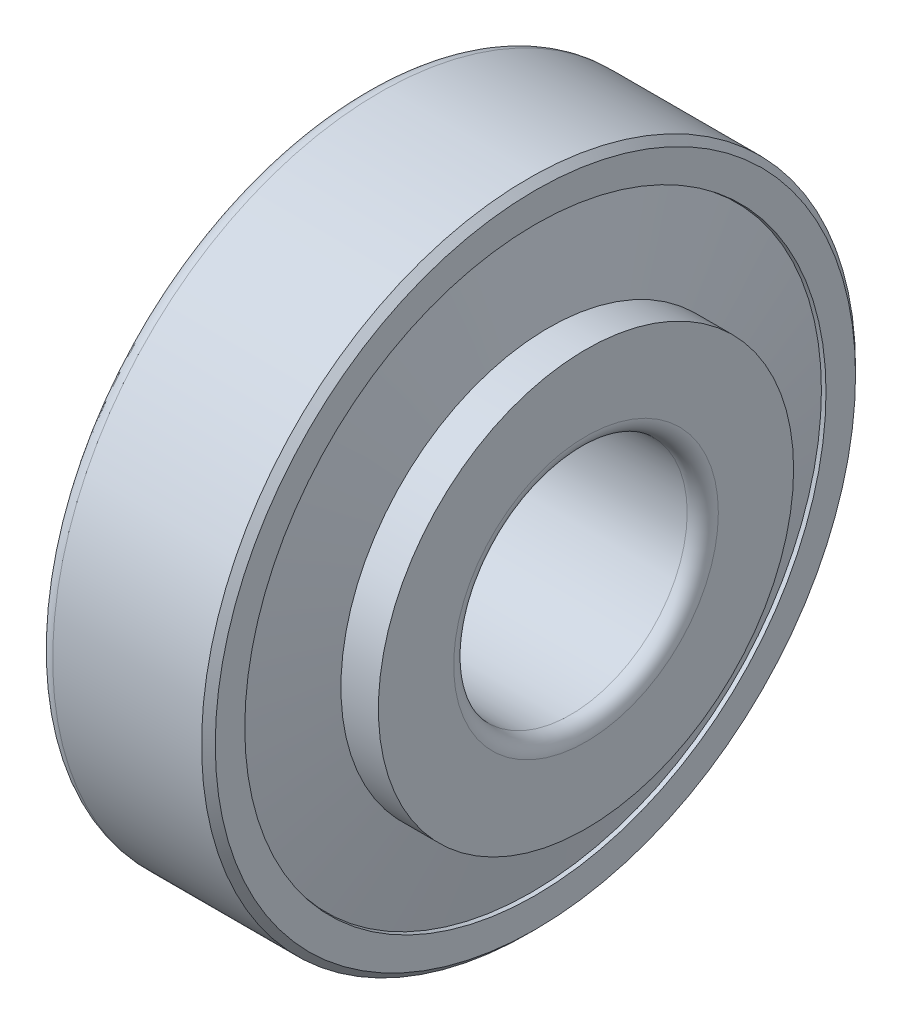
SolidWorks part; units mm, degrees
revolve "OuterRace" add sketch "OutRacSke" angle 360 about L5 other way angle 28.04 reverse direction yes
sketch "OutRacSke" plane through (0, 0, 0) normal (0, 0, 1) x (1, 0, 0)
  line L0 (-3.25, 18.6648) -> (-14.25, 16.636)
  line L1 (-14.25, 16.636) -> (-14.25, 20)
  line L2 (-13.25, 21) -> (-3.69, 21)
  line L3 (-3.69, 21) -> (-3.25, 20.56)
  line L4 (-3.25, 20.56) -> (-3.25, 18.6648)
  line L5 (-42.5, 0) -> (42.5, 0) construction
  arc A0 (-14.25, 20) -> (-13.25, 21) centre (-13.25, 20) cw
  dimension "D8" = 45
  dimension "Tangle" = 10.45
ref_plane "Plane1" through (0, 0, 0) normal (0, 0, 1) x (1, 0, 0)
ref_plane "Plane2" through (0, 0, 0) normal (0, 1, 0) x (1, 0, 0)
ref_plane "Plane3" through (0, 0, 0) normal (1, 0, 0) x (0, 0, -1)
sketch "Clipboard" plane through (0, 0, 0) normal (0, 0, 1) x (1, 0, 0)
  line L0 (0, 0) -> (10, 0) construction
  line L1 (0, 0) -> (33.2517, -1.1612)
  line L2 (0, 0) -> (14.9909, 0.5235)
  line L3 (0, 0) -> (41.9744, -1.4658)
  line L4 (0, 0) -> (-9.8985, -0.1728)
  line L5 (0, 0) -> (-6.075, 14.25)
  dimension "Roller_diameter" = 6.075
  dimension "cyl_len" = 9.9
sketch "RolDetSke" plane through (0, 0, 0) normal (0, 0, 1) x (1, 0, 0)
  line L0 (-12.6991, 13.9174) -> (-13.25, 16.9045)
  line L1 (-12.6991, 13.9174) -> (-2.9633, 15.7131)
  line L2 (-3.5142, 18.7002) -> (-2.9633, 15.7131)
  line L4 (-41.1331, 8.6731) -> (8.5425, 17.8351) construction
  line L5 (-3.5142, 18.7002) -> (-13.25, 16.9045)
  line L9 (-3.25, 18.6648) -> (-14.25, 16.636) construction
  dimension "Roller_diameter" = 6.075
  dimension "dy" = 16.9045
  dimension "D2" = 13.25
  dimension "cyl_len" = 9.9
revolve "RollerDetailed" [suppressed] add sketch "RolDetSke" angle 360 about L4 reverse direction yes
sketch "RolSimSke" plane through (0, 0, 0) normal (0, 0, 1) x (1, 0, 0)
  line L0 (0, 0) -> (-32, 0) construction
  line L1 (-13.25, 16.9045) -> (-3.5142, 18.7002)
  line L2 (-13.25, 16.9045) -> (-12.1481, 10.9303)
  line L3 (-12.1481, 10.9303) -> (-2.4123, 12.7259)
  line L4 (-3.5142, 18.7002) -> (-2.4123, 12.7259)
  dimension "Roller_diameter" = 6.075
  dimension "dy" = 16.9045
  dimension "dx" = 13.25
  dimension "Tangle" = 10.45
revolve "RollersSimplified" add sketch "RolSimSke" angle 360 about L0
ref_axis "Axis1" through (-50, 0, 0) along (1, 0, 0)
pattern_circular "RollersDetailed" [suppressed] count 2 every 180 about axis through (-50, 0, 0) along (1, 0, 0)
sketch "InsRacSke" plane through (0, 0, 0) normal (0, 0, 1) x (1, 0, 0)
  line L0 (-12.1986, 11.2341) -> (-13, 11.2341)
  line L1 (-14.25, 20) -> (-14.25, -20) construction
  line L2 (-13, 11.2341) -> (-13, 7.94)
  line L3 (-13, 7.94) -> (-12.56, 7.5)
  line L4 (-12.56, 7.5) -> (-1, 7.5)
  line L5 (0, 8.5) -> (0, 13.3334)
  line L6 (0, 13.3334) -> (-2.4068, 13.3334)
  line L7 (-2.4068, 13.3334) -> (-2.4068, 12.7259)
  line L8 (-2.4068, 12.7259) -> (-12.1426, 10.9303)
  line L9 (-12.1426, 10.9303) -> (-12.1986, 11.2341)
  line L10 (-42.5, 0) -> (42.5, 0) construction
  arc A0 (-1, 7.5) -> (0, 8.5) centre (-1, 8.5) ccw
  dimension "Tangle" = 10.45
  dimension "cyl_len" = 9.9
  dimension "dy" = 10.9303
  dimension "dx" = 12.1426
  dimension "D11" = 45
  dimension "D2" = 14.25
revolve "InnerRace" add sketch "InsRacSke" angle 360 about L10 reverse direction yes
sketch "CagSpiSke" plane through (0, 0, 0) normal (0, 0, 1) x (1, 0, 0)
  line L3 (-2.4765, 15.7187) -> (-12.6991, 13.8333)
  line L4 (-13.0239, 13.3616) -> (-12.877, 12.565)
  line L6 (-42.5, 0) -> (42.5, 0) construction
  arc A1 (-12.6991, 13.8333) -> (-13.0239, 13.3616) centre (-12.6256, 13.435) ccw
  dimension "Tangle" = 10.45
  dimension "radius" = 0.405
  dimension "dx" = 12.6991
  dimension "dy" = 13.8333
  dimension "offset" = 1.215
revolve "CageSpine" [suppressed] add sketch "CagSpiSke" angle 0.001 about L6 wall 1.0125
equation "\"OD@OutRacSke\" = \"Race_OD@Clipboard\""
equation "\"cup_SID@OutRacSke\" = \"Race_ID@Clipboard\""
equation "\"chamfer@OutRacSke\" = \"cup_width@OutRacSke\" / 25"
equation "\"offset@OutRacSke\" = \"OA_width@Clipboard\""
equation "\"D2@RolDetSke\" = \"offset@OutRacSke\" - \"cup_radius@OutRacSke\""
equation "\"dy@RolDetSke\" =  ( ( \"Race_ID@Clipboard\" / 2 ) + ( \"cup_radius@OutRacSke\" ) * tan(\"Tangle@OutRacSke\" * 3.141592654/180) ) * 1.005"
equation "\"cyl_len@RolDetSke\" = \"cyl_len@Clipboard\""
equation "\"Roller_diameter@RolDetSke\" = \"Roller_diameter@Clipboard\""
equation "\"dx@RolSimSke\" = \"offset@OutRacSke\" - \"cup_radius@OutRacSke\""
equation "\"dy@RolSimSke\" =  ( ( \"Race_ID@Clipboard\" / 2 ) + ( \"cup_radius@OutRacSke\" ) * tan(\"Tangle@OutRacSke\" * 3.141592654/180) ) * 1.005"
equation "\"Cyl_Len@RolSimSke\" = \"cyl_len@Clipboard\""
equation "\"Roller_diameter@RolSimSke\" = \"Roller_diameter@Clipboard\""
equation "\"Bore@InsRacSke\" = \"Bore@Clipboard\""
equation "\"Tangle@InsRacSke\" = \"Tangle@OutRacSke\""
equation "\"cyl_len@InsRacSke\" = \"cyl_len@Clipboard\""
equation "\"chamfer@InsRacSke\" = \"chamfer@OutRacSke\""
equation "\"D2@InsRacSke\" = \"OA_width@Clipboard\""
equation "\"dx@InsRacSke\" = \"offset@OutRacSke\" - \"cup_radius@OutRacSke\" -  (  \"Roller_diameter@Clipboard\" * 1.005 )  * sin(\"Tangle@InsRacSke\" * 3.141592654/180)"
equation "\"dy@InsRacSke\" = ( ( \"Race_ID@Clipboard\" / 2 ) + ( \"cup_radius@OutRacSke\" ) * tan(\"Tangle@OutRacSke\" * 3.141592654/180) ) * 1.005 -  ( \"Roller_diameter@Clipboard\" )  * cos(\"Tangle@InsRacSke\" * 3.141592654/180) "
equation "\"front_groove@InsRacSke\" = \"Groove_dp@InsRacSke\" / 2"
equation "\"Tangle@CagSpiSke\" = \"Tangle@OutRacSke\""
equation "\"dx@CagSpiSke\" = ( \"offset@OutRacSke\" - \"cup_radius@OutRacSke\" ) -  (  \"Roller_diameter@Clipboard\" / 2  )  * sin(\"Tangle@InsRacSke\" * 3.141592654/180)"
equation "\"dy@CagSpiSke\" = ( ( \"Race_ID@Clipboard\" / 2 ) + ( \"cup_radius@OutRacSke\" ) * tan(\"Tangle@OutRacSke\" * 3.141592654/180) )  -  ( \"Roller_diameter@Clipboard\" / 2 )  * cos(\"Tangle@InsRacSke\" * 3.141592654/180) "
equation "\"length@CagSpiSke\" = \"cyl_len@Clipboard\" * 1.05"
equation "\"offset@CagSpiSke\" = \"Roller_diameter@Clipboard\" / 5"
equation "\"radius@CagSpiSke\" = \"offset@CagSpiSke\" / 3"
equation "\"D3@CageSpine\" = \"Roller_diameter@Clipboard\" / 6"
equation "\"Max_count@Clipboard\" = int( 3.14159265 / atn(( \"Roller_diameter@Clipboard\" / 2) / sqr( \"dy@CagSpiSke\"  *  \"dy@CagSpiSke\" - ( \"Roller_diameter@Clipboard\" / 2) *  ( \"Roller_diameter@Clipboard\" / 2))))"
equation "\"Max_count@Clipboard\" = ((sgn( \"Max_count@Clipboard\" - \"Count@Clipboard\" )-1)*( \"Max_count@Clipboard\" - \"Count@Clipboard\" ))/-2+ \"Count@Clipboard\""
equation "\"Count@RollersDetailed\" = int( \"Show_count@Clipboard\" ) "
equation "\"Count@RollersDetailed\" = ((sgn( \"Count@RollersDetailed\" - \"Max_count@Clipboard\" )-1)*( \"Count@RollersDetailed\" - \"Max_count@Clipboard\" ))/-2+ \"Max_count@Clipboard\""
equation "\"Count@RollersDetailed\" = ((sgn( \"Count@RollersDetailed\" - \"Min_count@Clipboard\" )+1)*( \"Count@RollersDetailed\" - \"Min_count@Clipboard\"))/2 +\"Min_count@Clipboard\""
equation "\"Angle@RollersDetailed\" = 360.0 / \"Max_count@Clipboard\""
equation "\"Angle@CageSpine\" =  \"Angle@RollersDetailed\" * ( \"Count@RollersDetailed\" -1 + int( \"Count@RollersDetailed\" / \"Max_count@Clipboard\" ) )  + 0.001 -  int( \"Count@RollersDetailed\" / \"Max_count@Clipboard\" ) * 0.001"
equation "\"Angle@CageSpine\" =  \"Angle@CageSpine\" * int( \"Min_count@Clipboard\" / 2) + int(1 / \"Min_count@Clipboard\")  * 0.001"
equation "\"Tangle@RolSimSke\" = \"Tangle@OutRacSke\""
